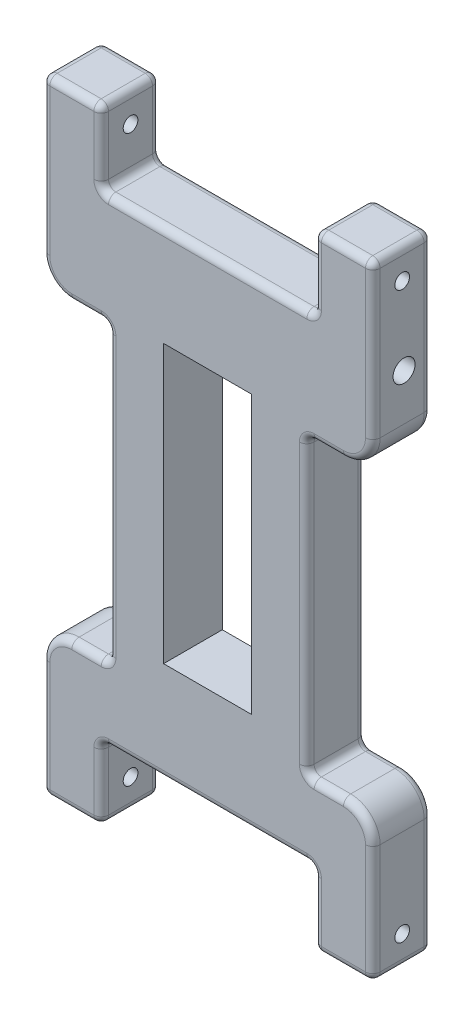
SolidWorks part; units mm, degrees
ref_plane "Front Plane" through (0, 0, 0) normal (0, 0, 1) x (1, 0, 0)
ref_plane "Top Plane" through (0, 0, 0) normal (0, 1, 0) x (1, 0, 0)
ref_plane "Right Plane" through (0, 0, 0) normal (1, 0, 0) x (0, 0, -1)
sketch "Sketch2" plane through (0, 0, 0) normal (0, 0, 1) x (1, 0, 0)
  line L0 (0, 0) -> (0, -42.5) construction
  line L1 (0, 0) -> (0, 42.5) construction
  line L2 (0, -42.5) -> (22.5, -42.5) construction
  line L3 (0, -42.5) -> (-22.5, -42.5) construction
  line L4 (-22.5, -42.5) -> (-22.5, -22.5)
  line L5 (-22.5, -22.5) -> (-13.5, -22.5)
  line L6 (-13.5, -22.5) -> (-13.5, 17.5)
  line L7 (-13.5, 17.5) -> (-22.5, 17.5)
  line L8 (-22.5, 17.5) -> (-22.5, 42.5)
  line L9 (-22.5, 42.5) -> (-14.5, 42.5)
  line L10 (-22.5, -42.5) -> (-14.5, -42.5)
  line L11 (-14.5, 42.5) -> (-14.5, 32.5)
  line L12 (-14.5, -42.5) -> (-14.5, -32.5)
  line L13 (-14.5, -32.5) -> (14.5, -32.5)
  line L14 (-14.5, 32.5) -> (14.5, 32.5)
  line L15 (14.5, -42.5) -> (14.5, -32.5)
  line L16 (14.5, 42.5) -> (14.5, 32.5)
  line L17 (22.5, -42.5) -> (14.5, -42.5)
  line L18 (22.5, 42.5) -> (14.5, 42.5)
  line L19 (22.5, 17.5) -> (22.5, 42.5)
  line L20 (13.5, 17.5) -> (22.5, 17.5)
  line L21 (13.5, -22.5) -> (13.5, 17.5)
  line L22 (22.5, -22.5) -> (13.5, -22.5)
  line L23 (22.5, -42.5) -> (22.5, -22.5)
  line L29 (-6, 18.8895) -> (6, -18.8895) construction
  line L30 (-6, -18.8895) -> (6, 18.8895) construction
  line L31 (6, -18.8895) -> (-6, -18.8895)
  line L32 (6, -18.8895) -> (6, 18.8895)
  line L33 (6, 18.8895) -> (-6, 18.8895)
  line L34 (-6, -18.8895) -> (-6, 18.8895)
  line L35 (6, -18.8895) -> (-6, 18.8895) construction
  line L36 (6, 18.8895) -> (-6, -18.8895) construction
  point P19 (0, 32.5)
  point P20 (0, -32.5)
  dimension "D1" = 42.5
  dimension "D2" = 42.5
  dimension "D3" = 13.6105
  dimension "D4" = 22.5
  dimension "D5" = 20
  dimension "D6" = 9
  dimension "D7" = 40
  dimension "D8" = 8
  dimension "D9" = 8
  dimension "D10" = 10
  dimension "D11" = 10
  dimension "D13" = 12
extrude "Boss-Extrude1" add sketch "Sketch2" along normal blind 8
fillet "Fillet1" radius 1 56 edges at (-14.5, -42.5, 4) (-14.5, -32.5, 4) (14.5, -32.5, 4) (14.5, -42.5, 4) (22.5, -42.5, 4) (13.5, -22.5, 4) (13.5, 17.5, 4) (22.5, 42.5, 4) (14.5, 42.5, 4) (14.5, 32.5, 4) (-14.5, 32.5, 4) (-14.5, 42.5, 4) (-22.5, 42.5, 4) (-13.5, 17.5, 4) (-13.5, -22.5, 4) (-22.5, -42.5, 4) (-22.5, -32.5, 8) (-18, -22.5, 8) (-13.5, -2.5, 8) (-18, 17.5, 8) (-22.5, 30, 8) (-18.5, 42.5, 8) (-14.5, 37.5, 8) (0, 32.5, 8) (14.5, 37.5, 8) (18.5, 42.5, 8) (22.5, 30, 8) (18, 17.5, 8) (13.5, -2.5, 8) (18, -22.5, 8) (22.5, -32.5, 8) (18.5, -42.5, 8) (14.5, -37.5, 8) (0, -32.5, 8) (-14.5, -37.5, 8) (-18.5, -42.5, 8) (-22.5, -32.5, 0) (-18, -22.5, 0) (-13.5, -2.5, 0) (-18, 17.5, 0) (-22.5, 30, 0) (-18.5, 42.5, 0) (-14.5, 37.5, 0) (0, 32.5, 0) (14.5, 37.5, 0) (18.5, 42.5, 0) (22.5, 30, 0) (18, 17.5, 0) (13.5, -2.5, 0) (18, -22.5, 0) (22.5, -32.5, 0) (18.5, -42.5, 0) (14.5, -37.5, 0) (0, -32.5, 0) (-14.5, -37.5, 0) (-18.5, -42.5, 0)
fillet "Fillet2" radius 4 12 edges at (22.2071, 17.7929, 0.2929) (22.2071, 17.7929, 7.7071) (-22.2071, 17.7929, 0.2929) (-22.2071, 17.7929, 7.7071) (-22.2071, -22.7929, 0.2929) (-22.2071, -22.7929, 7.7071) (22.2071, -22.7929, 0.2929) (22.2071, -22.7929, 7.7071) (22.5, -22.5, 4) (-22.5, -22.5, 4) (-22.5, 17.5, 4) (22.5, 17.5, 4)
sketch "Sketch3" plane through (-14.5, 0, 0) normal (1, 0, 0) x (0, 0, -1)
  circle A0 centre (-4, -38.5) radius 1
  dimension "D1" = 2
extrude "Cut-Extrude1" cut sketch "Sketch3" against normal through all both and the other way through all
mirror "Mirror1" about plane through (0, 0, 0) normal (0, 1, 0) of "Cut-Extrude1"
sketch "Sketch4" plane through (22.5, 0, 0) normal (1, 0, 0) x (0, 0, -1)
  line L0 (-7, 21.5) -> (-1, 21.5) construction
  circle A0 centre (-3.7427, 27.805) radius 1.5
  dimension "D1" = 3
  dimension "D2" = 6.305
extrude "Cut-Extrude2" cut sketch "Sketch4" against normal blind 10
